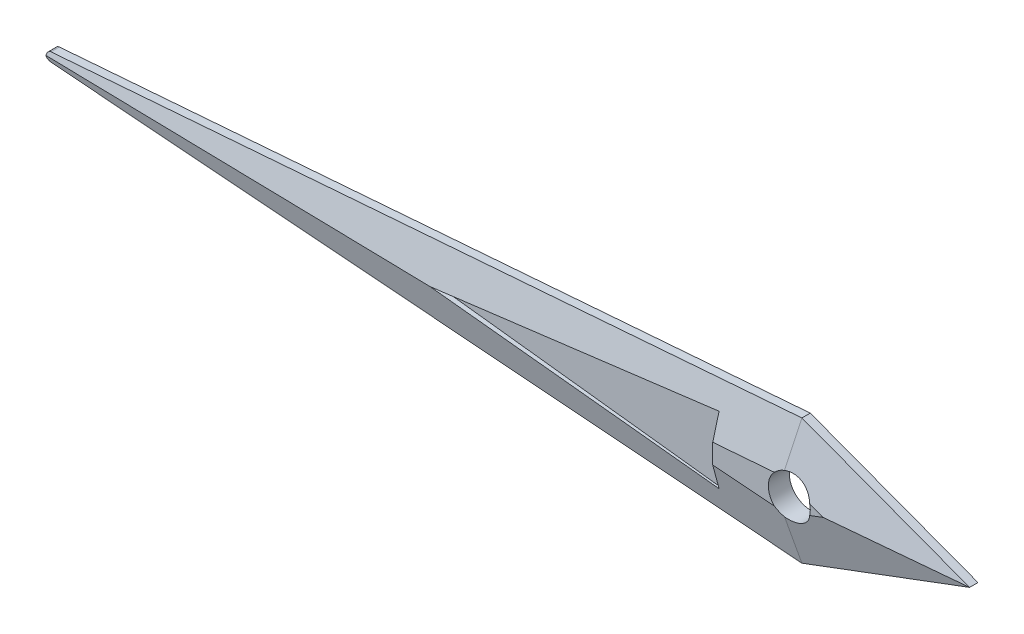
SolidWorks part; units mm, degrees
ref_plane "Front Plane" through (0, 0, 0) normal (0, 0, 1) x (1, 0, 0)
ref_plane "Top Plane" through (0, 0, 0) normal (0, 1, 0) x (1, 0, 0)
ref_plane "Right Plane" through (0, 0, 0) normal (1, 0, 0) x (0, 0, -1)
sketch "Sketch1" plane through (0, 0, 0) normal (0, 0, 1) x (1, 0, 0)
  line L1 (55, 0) -> (-55, 0) construction
  line L2 (0, -55) -> (0, 55) construction
  line L3 (0, 0.75) -> (-9, 0.05)
  line L4 (-9, 0.05) -> (-9, -0.05)
  line L5 (-9, -0.05) -> (0, -0.75)
  line L6 (0, -0.75) -> (2, 0)
  line L7 (0, 0.75) -> (2, 0)
  dimension "D4" = 0.05
extrude "Boss-Extrude1" add sketch "Sketch1" along normal blind 0.25
sketch "Sketch2" plane through (0, 0, 0.25) normal (0, 0, 1) x (1, 0, 0)
  circle A0 centre (0, 0) radius 0.25
  dimension "D1" = 0.5
extrude "Cut-Extrude1" cut sketch "Sketch2" against normal blind 0.25
chamfer "Chamfer1" distance 0.15 angle 75 2 edges at (1, 0.375, 0.25) (-4.5, 0.4, 0.25) first distance on face at (1, 0.375, 0.125) first distance on face at (-4.5, 0.4, 0.125)
chamfer "Chamfer2" distance 0.15 angle 75 2 edges at (0.6014, -0.5245, 0.25) (-3.0166, -0.5154, 0.25) first distance on face at (1.0406, -0.3598, 0.12) first distance on face at (-4.8066, -0.3761, 0.1253)
fillet "Fillet1" radius 0.05 2 edges at (-9, 0.05, 0.05) (-9, -0.05, 0.05)
sketch "Sketch3" plane through (0, 0, 0.25) normal (0, 0, 1) x (1, 0, 0)
  line L0 (-0.913, 0.4) -> (-0.913, -0.4)
  line L1 (-0.913, -0.4) -> (-4.324, 0)
  line L2 (0.1375, 0) -> (-0.1375, 0) construction
  line L3 (-4.324, 0) -> (-0.913, 0.4)
  dimension "D1" = 0.4
  dimension "D2" = 0.4
extrude "Cut-Extrude2" cut sketch "Sketch3" against normal blind 0.1
